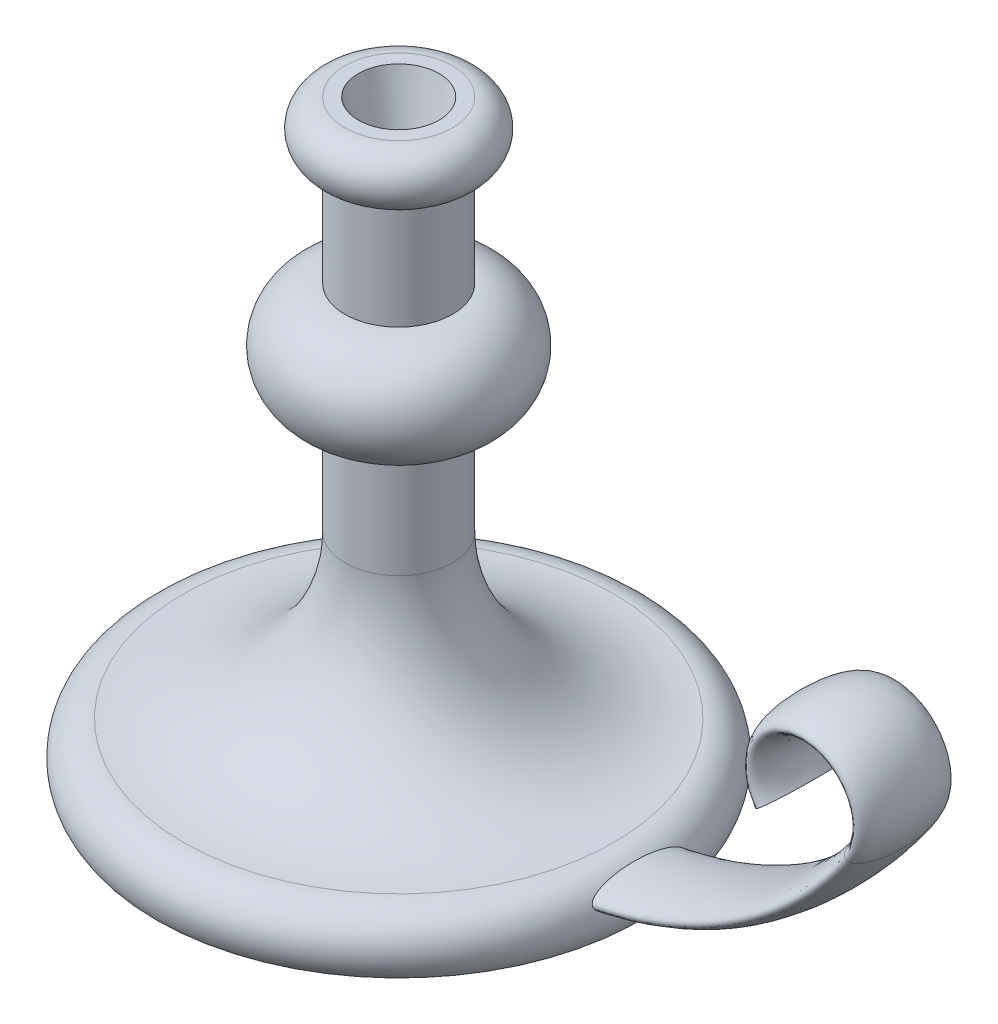
SolidWorks part; units mm, degrees
ref_plane "Front Plane" through (0, 0, 0) normal (0, 0, 1) x (1, 0, 0)
ref_plane "Top Plane" through (0, 0, 0) normal (0, 1, 0) x (1, 0, 0)
ref_plane "Right Plane" through (0, 0, 0) normal (1, 0, 0) x (0, 0, -1)
sketch "Sketch1" plane through (0, 0, 0) normal (0, 0, 1) x (1, 0, 0)
  line L0 (0, 0) -> (0, 220)
  line L1 (0, 220) -> (20, 220)
  line L2 (0, 0) -> (90, 0)
  line L3 (20, 200) -> (20, 160)
  line L4 (20, 120) -> (20, 80)
  arc A0 (20, 220) -> (20, 200) centre (20, 210) cw
  arc A1 (20, 160) -> (20, 120) centre (20, 140) cw
  arc A2 (20, 80) -> (80, 20) centre (80, 80) ccw
  arc A3 (80, 20) -> (90, 0) centre (80, 7.5) cw
  dimension "D4" = 10
  dimension "D5" = 20
  dimension "D7" = 60
  dimension "D8" = 12.5
  dimension "D1" = 20
  dimension "D2" = 220
  dimension "D3" = 90
  dimension "D6" = 40
  dimension "D9" = 80
revolve "Revolve1" add sketch "Sketch1" angle 360 about L0
sketch "Sketch2" plane through (0, 0, 0) normal (0, 0, 1) x (1, 0, 0)
  line L0 (0, 10) -> (60, 10)
  line L1 (0, 227.4356) -> (0, 175.1288) construction
  line L2 (-90, 0) -> (90, 0) construction
  arc A0 (60, 10) -> (183.5921, 75) centre (60, 160) ccw
  arc A1 (183.5921, 75) -> (150.6342, 75) centre (167.1131, 86.3333) ccw
  dimension "D2" = 150
  dimension "D4" = 20
  dimension "D1" = 60
  dimension "D3" = 65
  dimension "D5" = 10
sketch "Sketch3" plane through (0, 0, 0) normal (1, 0, 0) x (0, 0, -1)
  ellipse E0 centre (0, 10) end of major axis (17.5, 10) minor radius 5
  dimension "D1" = 35
  dimension "D2" = 10
sweep "Sweep1" add profiles "Sketch3" path "Sketch2"
sketch "Sketch4" plane through (0, 220, 0) normal (0, 1, 0) x (1, 0, 0)
  circle A0 centre (0, 0) radius 15
  dimension "D1" = 30
extrude "Cut-Extrude1" cut sketch "Sketch4" against normal blind 25 draft 15
